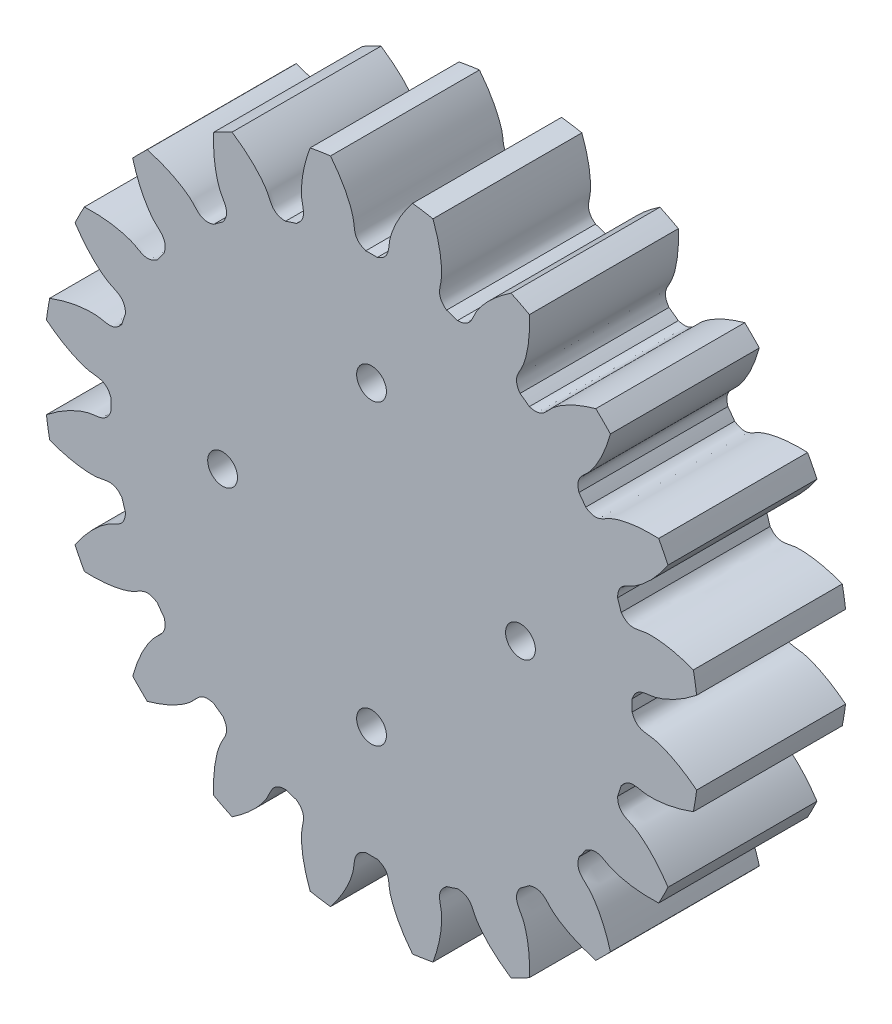
SolidWorks part; units mm, degrees
ref_plane "前视基准面" through (0, 0, 0) normal (0, 0, 1) x (1, 0, 0)
ref_plane "上视基准面" through (0, 0, 0) normal (0, 1, 0) x (1, 0, 0)
ref_plane "右视基准面" through (0, 0, 0) normal (1, 0, 0) x (0, 0, -1)
sketch "草图1" plane through (0, 0, 0) normal (0, 0, 1) x (1, 0, 0)
  circle A0 centre (0, 0) radius 66
extrude "凸台-拉伸1" add sketch "草图1" along normal blind 30
ref_axis "基准轴1" through (0, 0, -1.5) along (0, 0, 1)
sketch "草图2" plane through (0, 0, 0) normal (0, 0, 1) x (1, 0, 0)
  line L0 (0, 0) -> (0, 66) construction
  circle A0 centre (0, 0) radius 66 construction
  arc A1 (1.1599, 52.4872) -> (-1.1599, 52.4872) centre (0, 0) ccw
  arc A2 (19.0869, 74.9895) -> (-19.0869, 74.9895) centre (0, 0) ccw
  spline S0 degree 3 poles (1.1599, 52.4872) (3.6671, 53.3609) (3.3425, 55.1227) (3.6774, 56.8201) (3.7134, 56.9853) (3.7579, 57.1718) (3.8118, 57.3792) (3.8759, 57.6071) (3.9511, 57.8554) (4.0382, 58.1235) (4.138, 58.4111) (4.2514, 58.7179) (4.3791, 59.0433) (4.522, 59.3869) (4.6808, 59.7483) (4.8562, 60.1268) (5.0491, 60.5221) (5.2601, 60.9335) (5.49, 61.3604) (5.7395, 61.8023) (6.0092, 62.2586) (6.2999, 62.7285) (6.6121, 63.2115) (6.9466, 63.7068) (7.3039, 64.2138) (7.6846, 64.7317) (8.0893, 65.2598) (8.5185, 65.7973) (8.9729, 66.3435) (9.4528, 66.8975) (9.9589, 67.4586) (10.4914, 68.0259) (11.051, 68.5985) (11.638, 69.1757) (12.2528, 69.7564) (12.8958, 70.34) (13.5674, 70.9254) (14.2678, 71.5117) (14.9974, 72.098) (15.7564, 72.6834) (16.5451, 73.2669) (17.6488, 74.0498) (18.5036, 74.618) (19.0869, 74.9895) knots 0 0 0 0 0.165916 0.170906 0.176664 0.183189 0.190482 0.198542 0.207371 0.216967 0.22733 0.238462 0.250361 0.263027 0.276462 0.290664 0.305634 0.321371 0.337876 0.355149 0.37319 0.391998 0.411574 0.431917 0.453028 0.474907 0.497554 0.520968 0.54515 0.570099 0.595817 0.622302 0.649554 0.677575 0.706363 0.735918 0.766242 0.797333 0.829191 0.861818 0.895212 0.929373 1 1 1 1
  spline S1 degree 3 poles (-1.1599, 52.4872) (-3.6671, 53.3609) (-3.3425, 55.1227) (-3.6774, 56.8201) (-3.7134, 56.9853) (-3.7579, 57.1718) (-3.8118, 57.3792) (-3.8759, 57.6071) (-3.9511, 57.8554) (-4.0382, 58.1235) (-4.138, 58.4111) (-4.2514, 58.7179) (-4.3791, 59.0433) (-4.522, 59.3869) (-4.6808, 59.7483) (-4.8562, 60.1268) (-5.0491, 60.5221) (-5.2601, 60.9335) (-5.49, 61.3604) (-5.7395, 61.8023) (-6.0092, 62.2586) (-6.2999, 62.7285) (-6.6121, 63.2115) (-6.9466, 63.7068) (-7.3039, 64.2138) (-7.6846, 64.7317) (-8.0893, 65.2598) (-8.5185, 65.7973) (-8.9729, 66.3435) (-9.4528, 66.8975) (-9.9589, 67.4586) (-10.4914, 68.0259) (-11.051, 68.5985) (-11.638, 69.1757) (-12.2528, 69.7564) (-12.8958, 70.34) (-13.5674, 70.9254) (-14.2678, 71.5117) (-14.9974, 72.098) (-15.7564, 72.6834) (-16.5451, 73.2669) (-17.6488, 74.0498) (-18.5036, 74.618) (-19.0869, 74.9895) knots 0 0 0 0 0.165916 0.170906 0.176664 0.183189 0.190482 0.198542 0.207371 0.216967 0.22733 0.238462 0.250361 0.263027 0.276462 0.290664 0.305634 0.321371 0.337876 0.355149 0.37319 0.391998 0.411574 0.431917 0.453028 0.474907 0.497554 0.520968 0.54515 0.570099 0.595817 0.622302 0.649554 0.677575 0.706363 0.735918 0.766242 0.797333 0.829191 0.861818 0.895212 0.929373 1 1 1 1
extrude "切除-拉伸1" cut sketch "草图2" along normal through all
pattern_circular "阵列(圆周)1" count 20 every 18 about axis through (0, 0, -1.5) along (0, 0, 1) of "切除-拉伸1"
sketch "草图3" plane through (0, 0, 0) normal (0, 0, 1) x (1, 0, 0)
  circle A0 centre (0, 0) radius 60 construction
  dimension "Dn" = 120
sketch "草图4" plane through (0, 0, 30) normal (0, 0, 1) x (1, 0, 0)
  circle A0 centre (0, 0) radius 35
  circle A1 centre (-35, 0) radius 3
  circle A2 centre (-17.5, 30.3109) radius 3
  circle A3 centre (17.5, 30.3109) radius 3
  circle A4 centre (35, 0) radius 3
  circle A5 centre (17.5, -30.3109) radius 3
  circle A6 centre (-17.5, -30.3109) radius 3
  point P18 (0, 0)
  dimension "D1" = 70
  dimension "D2" = 6
extrude "切除-拉伸3" cut sketch "草图4" against normal blind 100 contours A1 | A2 | A3 | A4 | A5 | A6
sketch "草图5" plane through (0, 0, 30) normal (0, 0, 1) x (1, 0, 0)
  circle A0 centre (0, 0) radius 41.9495
extrude "凸台-拉伸3" add sketch "草图5" against normal blind 30
sketch "草图6" plane through (0, 0, 30) normal (0, 0, 1) x (1, 0, 0)
  circle A0 centre (0, 0) radius 30
  circle A1 centre (-30, 0) radius 3
  circle A2 centre (0, 30) radius 3
  circle A3 centre (30, 0) radius 3
  circle A4 centre (0, -30) radius 3
  point P13 (0, 0)
  dimension "D1" = 4
extrude "切除-拉伸4" cut sketch "草图6" against normal blind 30 contours A1 | A2 | A3 | A4
